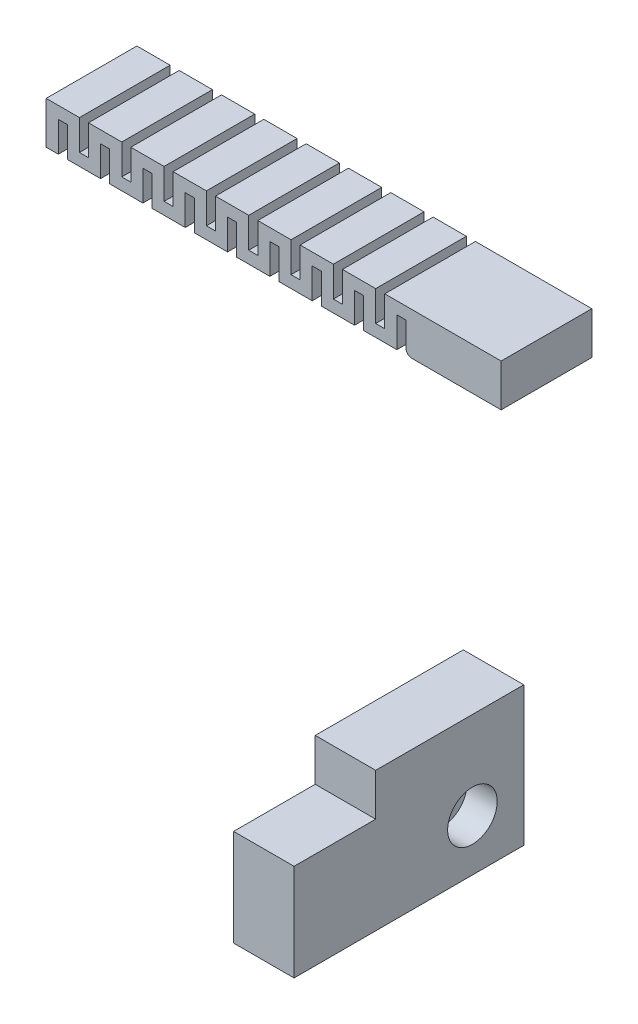
SolidWorks part; units mm, degrees
ref_plane "Front Plane" through (0, 0, 0) normal (0, 0, 1) x (1, 0, 0)
ref_plane "Top Plane" through (0, 0, 0) normal (0, 1, 0) x (1, 0, 0)
ref_plane "Right Plane" through (0, 0, 0) normal (1, 0, 0) x (0, 0, -1)
sketch "Sketch1" plane through (0, 0, 0) normal (0, 0, 1) x (1, 0, 0)
  line L1 (13.75, -3.5) -> (-13.75, -3.5)
  line L5 (0, 3.5) -> (0, -3.5) construction
  line L7 (19.25, 3.5) -> (19.25, -1.5)
  line L8 (19.25, -1.5) -> (20.75, -1.5)
  line L9 (20.75, -1.5) -> (20.75, 3.5)
  line L10 (20.75, 3.5) -> (26.25, 3.5)
  line L11 (26.25, 3.5) -> (26.25, -1.5)
  line L12 (26.25, -1.5) -> (27.75, -1.5)
  line L13 (27.75, -1.5) -> (27.75, 3.5)
  line L14 (27.75, 3.5) -> (33.25, 3.5)
  line L15 (33.25, 3.5) -> (33.25, -1.5)
  line L16 (33.25, -1.5) -> (34.75, -1.5)
  line L17 (34.75, -1.5) -> (34.75, 3.5)
  line L18 (34.75, 3.5) -> (40.25, 3.5)
  line L19 (40.25, 3.5) -> (40.25, -1.5)
  line L20 (36.75, -3.5) -> (36.75, 1.5)
  line L21 (36.75, 1.5) -> (38.25, 1.5)
  line L22 (38.25, 1.5) -> (38.25, -3.5)
  line L23 (38.25, -3.5) -> (43.75, -3.5)
  line L26 (15.75, 1.5) -> (17.25, 1.5)
  line L27 (17.25, 1.5) -> (17.25, -3.5)
  line L28 (17.25, -3.5) -> (22.75, -3.5)
  line L29 (22.75, -3.5) -> (22.75, 1.5)
  line L30 (22.75, 1.5) -> (24.25, 1.5)
  line L31 (24.25, 1.5) -> (24.25, -3.5)
  line L32 (24.25, -3.5) -> (29.75, -3.5)
  line L33 (29.75, -3.5) -> (29.75, 1.5)
  line L34 (29.75, 1.5) -> (31.25, 1.5)
  line L35 (31.25, 1.5) -> (31.25, -3.5)
  line L36 (31.25, -3.5) -> (36.75, -3.5)
  line L37 (43.75, -3.5) -> (43.75, 1.5)
  line L38 (43.75, 1.5) -> (45.25, 1.5)
  line L39 (45.25, 1.5) -> (45.25, -3.5)
  line L42 (47.25, 3.5) -> (41.75, 3.5)
  line L43 (41.75, 3.5) -> (41.75, -1.5)
  line L44 (41.75, -1.5) -> (40.25, -1.5)
  line L85 (13.75, -3.5) -> (15.75, -3.5)
  line L86 (15.75, -3.5) -> (15.75, 1.5)
  line L87 (47.25, 3.5) -> (47.25, -1.5)
  line L88 (47.25, -1.5) -> (48.75, -1.5)
  line L89 (48.75, -1.5) -> (48.75, 3.5)
  line L90 (48.75, 3.5) -> (54.25, 3.5)
  line L93 (52.25, -3.5) -> (52.25, 1.5)
  line L94 (52.25, 1.5) -> (50.75, 1.5)
  line L95 (50.75, 1.5) -> (50.75, -3.5)
  line L97 (45.25, -3.5) -> (50.75, -3.5)
  line L98 (-13.75, -3.5) -> (-15.75, -3.5)
  line L100 (-45.25, -3.5) -> (-50.75, -3.5)
  line L101 (-50.75, 1.5) -> (-50.75, -3.5)
  line L102 (-52.25, 1.5) -> (-50.75, 1.5)
  line L103 (-52.25, -3.5) -> (-52.25, 1.5)
  line L106 (-48.75, 3.5) -> (-54.25, 3.5)
  line L107 (-48.75, -1.5) -> (-48.75, 3.5)
  line L108 (-47.25, -1.5) -> (-48.75, -1.5)
  line L109 (-47.25, 3.5) -> (-47.25, -1.5)
  line L110 (-15.75, -3.5) -> (-15.75, 1.5)
  line L111 (-41.75, -1.5) -> (-40.25, -1.5)
  line L112 (-41.75, 3.5) -> (-41.75, -1.5)
  line L113 (-47.25, 3.5) -> (-41.75, 3.5)
  line L114 (-45.25, 1.5) -> (-45.25, -3.5)
  line L115 (-43.75, 1.5) -> (-45.25, 1.5)
  line L116 (-43.75, -3.5) -> (-43.75, 1.5)
  line L117 (-31.25, -3.5) -> (-36.75, -3.5)
  line L118 (-31.25, 1.5) -> (-31.25, -3.5)
  line L119 (-29.75, 1.5) -> (-31.25, 1.5)
  line L120 (-29.75, -3.5) -> (-29.75, 1.5)
  line L121 (-24.25, -3.5) -> (-29.75, -3.5)
  line L122 (-24.25, 1.5) -> (-24.25, -3.5)
  line L123 (-22.75, 1.5) -> (-24.25, 1.5)
  line L124 (-22.75, -3.5) -> (-22.75, 1.5)
  line L125 (-17.25, -3.5) -> (-22.75, -3.5)
  line L126 (-17.25, 1.5) -> (-17.25, -3.5)
  line L127 (-15.75, 1.5) -> (-17.25, 1.5)
  line L128 (-38.25, -3.5) -> (-43.75, -3.5)
  line L129 (-38.25, 1.5) -> (-38.25, -3.5)
  line L130 (-36.75, 1.5) -> (-38.25, 1.5)
  line L131 (-36.75, -3.5) -> (-36.75, 1.5)
  line L132 (-40.25, 3.5) -> (-40.25, -1.5)
  line L133 (-34.75, 3.5) -> (-40.25, 3.5)
  line L134 (-34.75, -1.5) -> (-34.75, 3.5)
  line L135 (-33.25, -1.5) -> (-34.75, -1.5)
  line L136 (-33.25, 3.5) -> (-33.25, -1.5)
  line L137 (-27.75, 3.5) -> (-33.25, 3.5)
  line L138 (-27.75, -1.5) -> (-27.75, 3.5)
  line L139 (-26.25, -1.5) -> (-27.75, -1.5)
  line L140 (-26.25, 3.5) -> (-26.25, -1.5)
  line L141 (-20.75, 3.5) -> (-26.25, 3.5)
  line L142 (-20.75, -1.5) -> (-20.75, 3.5)
  line L143 (-19.25, -1.5) -> (-20.75, -1.5)
  line L144 (-19.25, 3.5) -> (-19.25, -1.5)
  line L145 (-54.25, 3.5) -> (-54.25, -1.5)
  line L146 (-54.25, -1.5) -> (-55.75, -1.5)
  line L147 (-55.75, -1.5) -> (-55.75, 3.5)
  line L148 (-55.75, 3.5) -> (-61.25, 3.5)
  line L149 (-61.25, 3.5) -> (-61.25, -1.5)
  line L150 (-61.25, -1.5) -> (-62.75, -1.5)
  line L151 (-62.75, -1.5) -> (-62.75, 3.5)
  line L158 (-64.75, -3.5) -> (-59.25, -3.5)
  line L159 (-57.75, -3.5) -> (-57.75, 1.5)
  line L160 (-57.75, 1.5) -> (-59.25, 1.5)
  line L161 (-59.25, 1.5) -> (-59.25, -3.5)
  line L163 (54.25, 3.5) -> (54.25, -1.5)
  line L164 (54.25, -1.5) -> (55.75, -1.5)
  line L165 (55.75, -1.5) -> (55.75, 3.5)
  line L166 (55.75, 3.5) -> (61.25, 3.5)
  line L177 (59.25, -3.5) -> (59.25, 1.5)
  line L178 (59.25, 1.5) -> (57.75, 1.5)
  line L179 (57.75, 1.5) -> (57.75, -3.5)
  line L183 (57.75, -3.5) -> (52.25, -3.5)
  line L184 (-62.75, 3.5) -> (-68.25, 3.5)
  line L185 (61.25, 3.5) -> (61.25, -1.5)
  line L186 (61.25, -1.5) -> (62.75, -1.5)
  line L187 (62.75, -1.5) -> (62.75, 3.5)
  line L190 (59.25, -3.5) -> (64.75, -3.5)
  line L191 (-57.75, -3.5) -> (-52.25, -3.5)
  line L192 (13.75, 3.5) -> (19.25, 3.5)
  line L194 (62.75, 3.5) -> (68.25, 3.5)
  line L197 (-19.25, 3.5) -> (-13.75, 3.5)
  line L199 (68.25, 3.5) -> (68.25, -1.5)
  line L205 (73.25, -3.5) -> (73.25, 1.5)
  line L206 (73.25, 1.5) -> (71.75, 1.5)
  line L207 (71.75, 1.5) -> (71.75, -3.5)
  line L208 (71.75, -3.5) -> (66.25, -3.5)
  line L209 (66.25, -3.5) -> (66.25, 1.5)
  line L210 (66.25, 1.5) -> (64.75, 1.5)
  line L211 (64.75, 1.5) -> (64.75, -3.5)
  line L212 (68.25, -1.5) -> (69.75, -1.5)
  line L213 (69.75, -1.5) -> (69.75, 3.5)
  line L214 (69.75, 3.5) -> (75.25, 3.5)
  line L215 (75.25, 3.5) -> (75.25, -3.5)
  line L216 (75.25, -3.5) -> (73.25, -3.5)
  line L217 (-64.75, -3.5) -> (-64.75, 1.5)
  line L218 (-64.75, 1.5) -> (-66.25, 1.5)
  line L219 (-66.25, 1.5) -> (-66.25, -3.5)
  line L220 (-66.25, -3.5) -> (-71.75, -3.5)
  line L221 (-71.75, -3.5) -> (-71.75, 1.5)
  line L222 (-71.75, 1.5) -> (-73.25, 1.5)
  line L223 (-73.25, 1.5) -> (-73.25, -3.5)
  line L224 (-68.25, 3.5) -> (-68.25, -1.5)
  line L225 (-68.25, -1.5) -> (-69.75, -1.5)
  line L226 (-69.75, -1.5) -> (-69.75, 3.5)
  line L227 (-69.75, 3.5) -> (-75.25, 3.5)
  line L228 (-75.25, 3.5) -> (-75.25, -3.5)
  line L229 (-75.25, -3.5) -> (-73.25, -3.5)
  line L230 (-13.75, 3.5) -> (13.75, 3.5)
  point P0 (0, 0)
  point P47 (0, 0)
  point P53 (0, 0)
  point P123 (0, 0)
  dimension "D3" = 2
  dimension "D4" = 7
  dimension "D5" = 2
  dimension "D6" = 2
  dimension "D7" = 2
  dimension "D8" = 1.5
  dimension "D9" = 2
  dimension "D10" = 2
  dimension "D11" = 2
  dimension "D12" = 2
  dimension "D13" = 5.5
  dimension "D14" = 2
  dimension "D15" = 7
  dimension "D16" = 2
  dimension "D17" = 1.5
  dimension "D18" = 2
  dimension "D19" = 2
  dimension "D20" = 5.5
  dimension "D21" = 27.5
extrude "Boss-Extrude1" add sketch "Sketch1" along normal blind 62.5
sketch "Sketch2" plane through (0, 0, 62.5) normal (0, 0, 1) x (1, 0, 0)
  line L1 (15.75, -3.5) -> (-15.75, -3.5)
  line L2 (15.75, -3.5) -> (15.75, 3.5)
  line L3 (15.75, 3.5) -> (-15.75, 3.5)
  line L4 (-15.75, -3.5) -> (-15.75, 3.5)
  line L5 (15.75, -3.5) -> (-15.75, 3.5) construction
  line L6 (15.75, 3.5) -> (-15.75, -3.5) construction
  line L8 (-15.75, 1.5) -> (-15.75, -3.5) construction
  point P0 (0, 0)
  dimension "D1" = 7
extrude "Boss-Extrude2" add sketch "Sketch2" along normal blind 20
sketch "Sketch3" plane through (15.75, 0, 0) normal (1, 0, 0) x (0, 0, -1)
  line L1 (-67.5, 3.5) -> (-82.5, 3.5)
  line L3 (-67.5, -3.5) -> (-82.5, -3.5)
  line L4 (-82.5, 3.5) -> (-82.5, -3.5)
  line L5 (-82.5, -3.5) -> (-82.5, 3.5) construction
  line L7 (-67.5, 3.5) -> (-67.5, -3.5)
  line L8 (-62.5, -3.5) -> (-62.5, 3.5) construction
  line L9 (-82.5, -3.5) -> (0, -3.5) construction
  dimension "D1" = 7
  dimension "D2" = 5
extrude "Boss-Extrude3" add sketch "Sketch3" along normal blind 19
mirror "Mirror1" about plane through (0, 0, 0) normal (1, 0, 0) of "Boss-Extrude3"
sketch "Sketch4" plane through (34.75, 0, 0) normal (1, 0, 0) x (0, 0, -1)
  line L0 (-82.5, 3.5) -> (-82.5, -3.5) construction
  line L1 (-67.5, 3.5) -> (-82.5, 3.5)
  line L2 (-67.5, 3.5) -> (-67.5, -11.5)
  line L3 (-67.5, -11.5) -> (-82.5, -11.5)
  line L4 (-82.5, 3.5) -> (-82.5, -11.5)
  line L5 (-67.5, -3.5) -> (-67.5, 3.5) construction
  line L6 (-67.5, 3.5) -> (-82.5, 3.5) construction
  dimension "D1" = 15
extrude "Boss-Extrude4" add sketch "Sketch4" along normal blind 10
mirror "Mirror2" about plane through (0, 0, 0) normal (1, 0, 0) of "Boss-Extrude4"
sketch "Sketch5" plane through (44.75, 0, 0) normal (1, 0, 0) x (0, 0, -1)
  line L0 (-75, 3.5) -> (-75, -11.5) construction
  line L1 (-67.5, 3.5) -> (-82.5, 3.5) construction
  line L2 (-82.5, -11.5) -> (-67.5, -11.5) construction
  circle A0 centre (-75, -4) radius 3.7137
  dimension "D1" = 7.4275
extrude "Cut-Extrude1" cut sketch "Sketch5" against normal blind 7
mirror "Mirror3" about plane through (0, 0, 0) normal (1, 0, 0) of "Cut-Extrude1"
fillet "Fillet1" radius 1 22 edges at (-34.75, -7.5, 82.5) (-25.25, -3.5, 67.5) (0, -3.5, 82.5) (25.25, -3.5, 67.5) (34.75, -11.5, 75) (-34.75, -11.5, 75) (-34.75, -7.5, 67.5) (34.75, -7.5, 82.5) (34.75, -7.5, 67.5) (-44.75, 3.5, 75) (34.75, -3.5, 75) (-34.75, -3.5, 75) (44.75, -4, 82.5) (44.75, -11.5, 75) (44.75, 3.5, 75) (44.75, -4, 67.5) (39.75, -11.5, 67.5) (-39.75, -11.5, 67.5) (-44.75, -11.5, 75) (-44.75, -4, 67.5) (-44.75, -4, 82.5) (0, 3.5, 82.5)
fillet "Fillet2" radius 1 2 edges at (15.75, -3.5, 34.25) (-15.75, -3.5, 34.25)
ref_plane "Plane1" through (45.25, 0, 0) normal (1, 0, 0) x (0, 0, -1)
sketch "Sketch7" plane through (45.25, 0, 0) normal (1, 0, 0) x (0, 0, -1)
  line L0 (-68.5, -11.5) -> (-82.5, -11.5) construction
  line L1 (-66.5, -12.5) -> (-91, -12.5)
  line L2 (-66.5, -12.5) -> (-66.5, 10.5)
  line L5 (-67.5, 3.5) -> (-67.5, -10.5) construction
  line L14 (-91, 10.5) -> (-66.5, 10.5)
  line L15 (-91, 10.5) -> (-91, 3.5)
  line L16 (-91, 3.5) -> (-104.5, 3.5)
  line L17 (-104.5, 3.5) -> (-104.5, -12.5)
  line L18 (-104.5, -12.5) -> (-91, -12.5)
  circle A1 centre (-75, -4) radius 2.55
  circle A2 centre (-75, -4) radius 4.1
  dimension "D1" = 5.1
  dimension "D2" = 8.2
  dimension "D3" = 1
  dimension "D4" = 1
  dimension "D5" = 16
  dimension "D6" = 7
  dimension "D7" = 13.5
  dimension "D8" = 29.5
extrude "Boss-Extrude5" add sketch "Sketch7" along normal blind 10 separate body contours A2 region at (45.25, -1.8223, 84.67)
extrude "Boss-Extrude6" add sketch "Sketch7<3>" along normal blind 5 contours A2 A1 region at (45.25, -4, 78.984)
sketch "Sketch7<3>" plane through (45.25, 0, 0) normal (1, 0, 0) x (0, 0, -1) same geometry as "Sketch7"
sketch "Sketch8" plane through (0, 3.5, 0) normal (0, 1, 0) x (1, 0, 0)
  line L0 (0, 0) -> (0, -62.4553) construction
  line L1 (73.25, -6.25) -> (81.25, -6.25)
  line L2 (73.25, -6.25) -> (73.25, -56.25)
  line L3 (73.25, -56.25) -> (81.25, -56.25)
  line L4 (81.25, -6.25) -> (81.25, -56.25)
  line L5 (75.25, 0) -> (69.75, 0) construction
  line L6 (0, -31.2277) -> (75.25, -31.25) construction
  line L7 (75.25, -62.5) -> (75.25, 0) construction
  dimension "D1" = 62.4553
  dimension "D2" = 50
  dimension "D3" = 6.25
  dimension "D4" = 2
  dimension "D5" = 8
extrude "Boss-Extrude7" add sketch "Sketch8" against normal blind 7
sketch "Sketch9" plane through (0, 3.5, 0) normal (0, 1, 0) x (1, 0, 0)
  line L0 (75.25, -6.25) -> (75.25, -56.25) construction
  line L1 (75.75, -11.25) -> (78.75, -11.25)
  line L2 (75.75, -11.25) -> (75.75, -51.25)
  line L3 (75.75, -51.25) -> (78.75, -51.25)
  line L4 (78.75, -11.25) -> (78.75, -51.25)
  line L5 (81.25, -31.25) -> (78.75, -31.25) construction
  line L6 (81.25, -56.25) -> (81.25, -6.25) construction
  dimension "D1" = 2.5
  dimension "D2" = 3
  dimension "D3" = 40
extrude "Cut-Extrude2" cut sketch "Sketch9" against normal blind 10
sketch "Sketch10" plane through (0, 3.5, 0) normal (0, 1, 0) x (1, 0, 0)
  line L0 (0, 0) -> (86.3657, 0)
  line L1 (86.3657, 0) -> (86.3657, -92.9376)
  line L2 (86.3657, -92.9376) -> (-81.1751, -92.9376)
  line L3 (-81.1751, -92.9376) -> (-81.1751, -15)
  line L4 (-81.1751, -15) -> (0, -15)
  line L5 (0, -15) -> (0, 0)
  dimension "D1" = 15
  dimension "D2" = 167.5408
  dimension "D3" = 81.1751
  dimension "D4" = 77.9376
extrude "Cut-Extrude3" cut sketch "Sketch10" against normal through all
